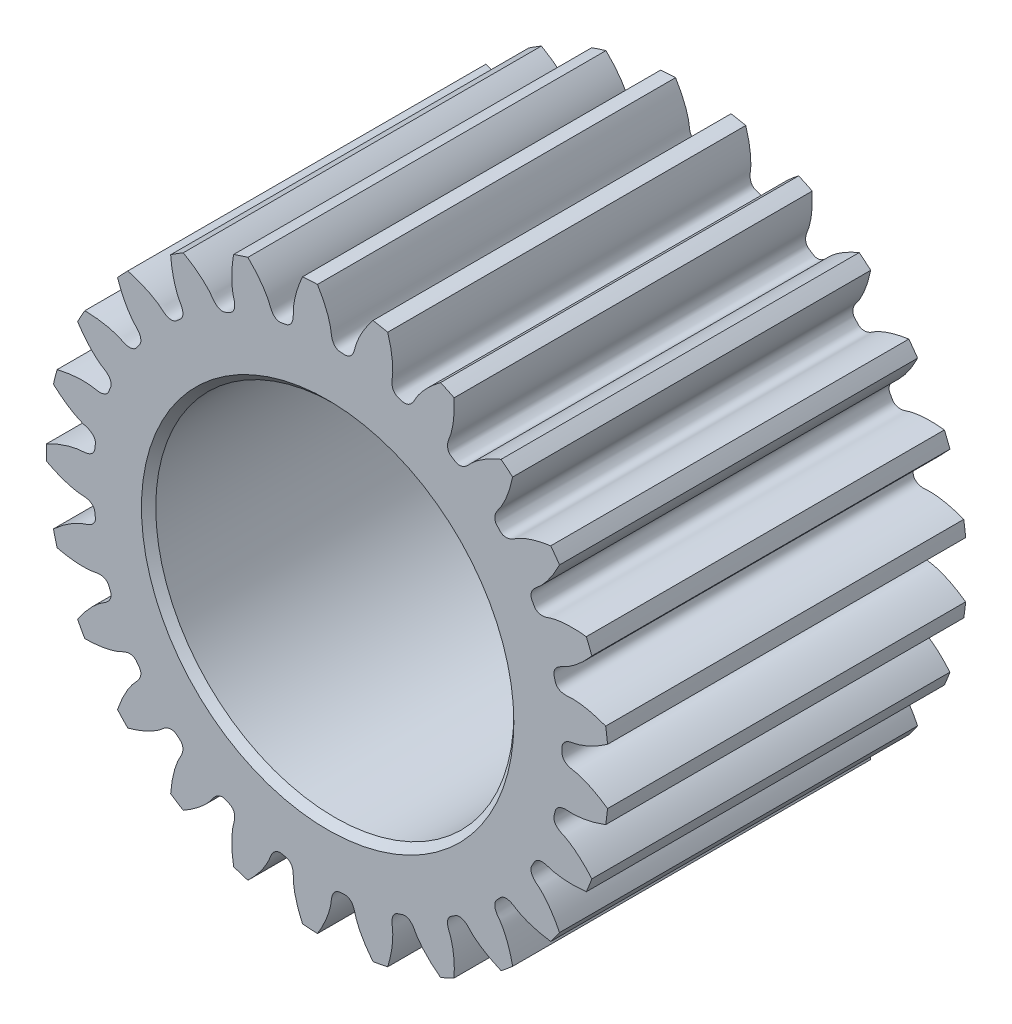
SolidWorks part; units mm, degrees
ref_plane "Front Plane" through (0, 0, 0) normal (0, 0, 1) x (1, 0, 0)
ref_plane "Top Plane" through (0, 0, 0) normal (0, 1, 0) x (1, 0, 0)
ref_plane "Right Plane" through (0, 0, 0) normal (1, 0, 0) x (0, 0, -1)
ref_axis "Axis1" through (0, 0, 55) along (0, 0, -1)
sketch "SketchRevolveSun_Fixed02" plane through (0, 0, 0) normal (1, 0, 0) x (0, 0, -1)
  line L0 (0, 0) -> (25.4, 0) construction
  line L1 (-6.35, 0) -> (-6.35, 9.9761)
  line L2 (-6.35, 9.9761) -> (6.35, 9.9761)
  line L3 (6.35, 9.9761) -> (6.35, 0)
  line L4 (6.35, 0) -> (-6.35, 0)
  dimension "Side1" = 6.35
  dimension "OutsideRadius" = 9.9761
  dimension "Side2" = 6.35
revolve "Sun_Fixed02" add sketch "SketchRevolveSun_Fixed02" angle 360 about L0
sketch "SketchToothSun_Fixed02" plane through (0, 0, 0) normal (0, 0, 1) x (1, 0, 0)
  arc A0 (9.9619, 1.0107) -> (9.9619, -1.0107) centre (0, 0) cw
  spline S0 degree 3 poles (9.9619, -1.0107) (9.8541, -0.9333) (9.7102, -0.8383) (9.5288, -0.7338) (9.4309, -0.681) (9.3379, -0.6343) (9.2501, -0.5933) (9.1677, -0.5577) (9.091, -0.5272) (9.0203, -0.5013) (8.9556, -0.4797) (8.8972, -0.4621) (8.8452, -0.448) (8.7998, -0.4371) (8.7378, -0.4239) (8.6833, -0.4167) (8.6358, -0.4057) (8.6156, -0.4005) (8.5958, -0.3948) (8.5764, -0.3887) (8.5574, -0.3819) (8.5388, -0.3746) (8.5204, -0.3667) (8.5024, -0.358) (8.4845, -0.3486) (8.4669, -0.3382) (8.4495, -0.3267) (8.4322, -0.314) (8.4151, -0.2998) (8.3983, -0.2838) (8.3819, -0.2659) (8.3661, -0.2457) (8.3514, -0.223) (8.3381, -0.1977) (8.327, -0.1697) (8.3186, -0.1393) (8.3141, -0.1091) (8.3121, -0.0624) (8.3144, 0) (8.3121, 0.0624) (8.3141, 0.1091) (8.3186, 0.1393) (8.327, 0.1697) (8.3381, 0.1977) (8.3514, 0.223) (8.3661, 0.2457) (8.3819, 0.2659) (8.3983, 0.2838) (8.4151, 0.2998) (8.4322, 0.314) (8.4495, 0.3267) (8.4669, 0.3382) (8.4845, 0.3486) (8.5024, 0.358) (8.5204, 0.3667) (8.5388, 0.3746) (8.5574, 0.3819) (8.5764, 0.3887) (8.5958, 0.3948) (8.6156, 0.4005) (8.6358, 0.4057) (8.6833, 0.4167) (8.7378, 0.4239) (8.7998, 0.4371) (8.8452, 0.448) (8.8972, 0.4621) (8.9556, 0.4797) (9.0203, 0.5013) (9.091, 0.5272) (9.1677, 0.5577) (9.2501, 0.5933) (9.3379, 0.6343) (9.4309, 0.681) (9.5288, 0.7338) (9.7102, 0.8383) (9.8541, 0.9333) (9.9619, 1.0107) knots 0 0 0 0 0.097255 0.12617 0.153333 0.178744 0.202402 0.224308 0.244461 0.262862 0.27951 0.294406 0.307549 0.31894 0.328579 0.354008 0.359183 0.364276 0.369295 0.374255 0.379167 0.38405 0.388922 0.393804 0.398723 0.403708 0.408793 0.414017 0.419422 0.425055 0.430965 0.437198 0.443793 0.450772 0.458134 0.46584 0.473813 0.480451 0.5 0.519549 0.526187 0.53416 0.541866 0.549228 0.556207 0.562802 0.569035 0.574945 0.580578 0.585983 0.591207 0.596292 0.601277 0.606196 0.611078 0.61595 0.620833 0.625745 0.630705 0.635724 0.640817 0.645992 0.671421 0.68106 0.692451 0.705594 0.72049 0.737138 0.755539 0.775692 0.797598 0.821256 0.846667 0.87383 0.902745 1 1 1 1
extrude "ToothExtrudeCutSun_Fixed02" cut sketch "SketchToothSun_Fixed02" against normal blind 6.35 and the other way blind 6.35
ref_axis "Axis2" through (11.0125, 0, 0) along (-1, 0, 0)
ref_plane "Plane1" through (0, 0, 0) normal (0, 0, -1) x (1, 0, 0)
pattern_circular "PatternSun_Fixed02" count 25 every 14.4 about axis through (0, 0, 55) along (0, 0, -1) of "ToothExtrudeCutSun_Fixed02"
sketch "BoreRevolveSketch" plane through (0, 0, 0) normal (1, 0, 0) x (0, 0, -1)
  line L0 (0, 0) -> (25.4, 0) construction
  line L1 (-6.35, 0) -> (6.35, 0)
  line L2 (6.35, 0) -> (6.35, 6.604)
  line L3 (6.35, 6.604) -> (6.096, 6.35)
  line L4 (6.096, 6.35) -> (-6.096, 6.35)
  line L5 (-6.096, 6.35) -> (-6.35, 6.604)
  line L6 (-6.35, 6.604) -> (-6.35, 0)
  dimension "BoreSide1" = 6.35
  dimension "TaperSide1" = 6.604
  dimension "Chamfer1X" = 0.254
  dimension "Chamfer1Y" = 0.254
  dimension "BoreSide2" = 6.35
  dimension "TaperSide2" = 6.604
revolve "BoreRevolveCut" cut sketch "BoreRevolveSketch" angle 360 about L0
sketch "AuxiliarySketchSun_Fixed02" plane through (0, 0, 0) normal (0, 0, 1) x (1, 0, 0)
  circle A0 centre (0, 0) radius 9.2371 construction
  circle A1 centre (0, 0) radius 8.6801 construction
  circle A2 centre (0, 0) radius 8.7251 construction
  circle A3 centre (0, 0) radius 9.9761 construction
  circle A4 centre (0, 0) radius 8.3134 construction
  dimension "PitchDiameter" = 18.4743
  dimension "BaseDiameter" = 17.3602
  dimension "FormDiameter" = 17.4502
  dimension "MajorDiameter" = 19.9522
  dimension "MinorDiameter" = 16.6269
